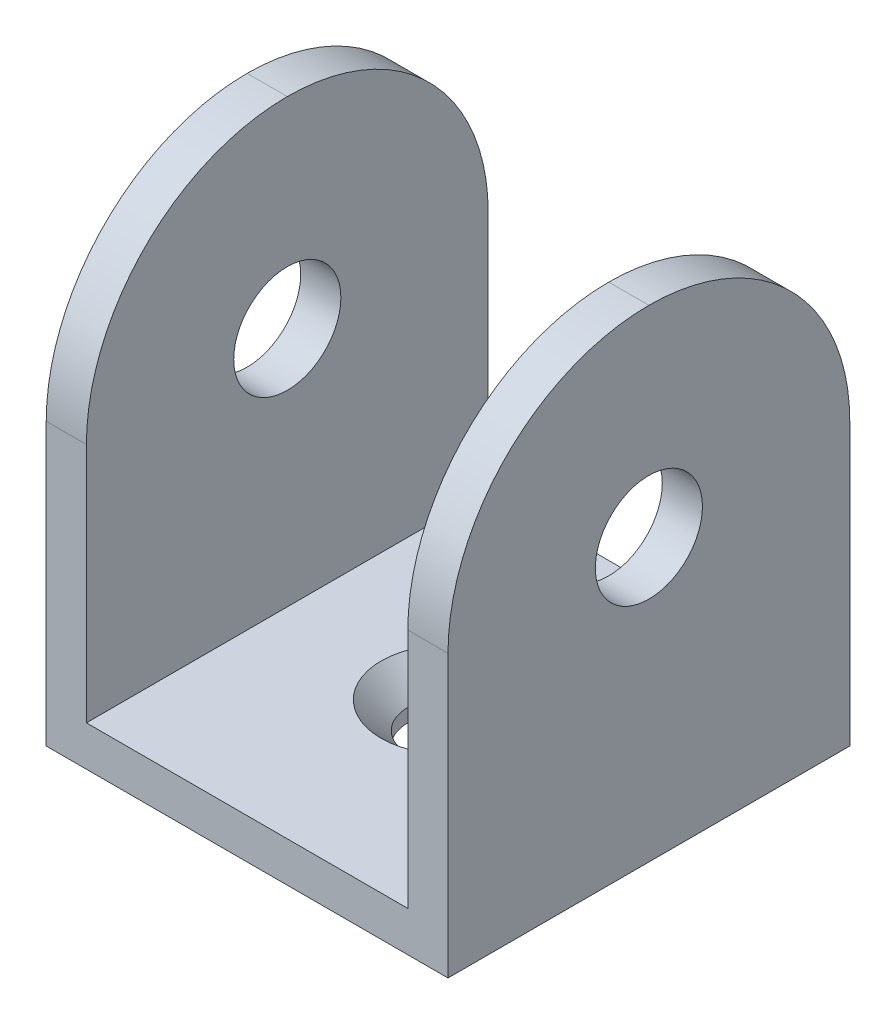
SolidWorks part; units mm, degrees
ref_plane "Alzado" through (0, 0, 0) normal (0, 0, 1) x (1, 0, 0)
ref_plane "Planta" through (0, 0, 0) normal (0, 1, 0) x (1, 0, 0)
ref_plane "Vista lateral" through (0, 0, 0) normal (1, 0, 0) x (0, 0, -1)
sketch "Croquis1" plane through (0, 0, 0) normal (0, 1, 0) x (1, 0, 0)
  line L1 (15, -15) -> (-15, -15)
  line L2 (15, -15) -> (15, 15)
  line L3 (15, 15) -> (-15, 15)
  line L4 (-15, -15) -> (-15, 15)
  line L5 (15, -15) -> (-15, 15) construction
  line L6 (15, 15) -> (-15, -15) construction
  point P0 (0, 0)
  dimension "D1" = 30
extrude "Saliente-Extruir1" add sketch "Croquis1" along normal blind 3
sketch "Croquis2" plane through (0, 3, 0) normal (0, 1, 0) x (1, 0, 0)
  line L0 (-15, -15) -> (15, -15) construction
  line L1 (-15, 15) -> (-12, 15)
  line L2 (-15, 15) -> (-15, -15)
  line L3 (-15, -15) -> (-12, -15)
  line L4 (-12, 15) -> (-12, -15)
  line L6 (15, 15) -> (12, 15)
  line L7 (15, 15) -> (15, -15)
  line L8 (15, -15) -> (12, -15)
  line L9 (12, 15) -> (12, -15)
  dimension "D1" = 3
extrude "Saliente-Extruir2" add sketch "Croquis2" along normal blind 33
fillet "Redondeo1" radius 15 4 edges at (-13.5, 36, -15) (13.5, 36, -15) (13.5, 36, 15) (-13.5, 36, 15)
sketch "Croquis3" plane through (15, 0, 0) normal (1, 0, 0) x (0, 0, -1)
  circle A0 centre (0, 21) radius 4
  dimension "D1" = 8
extrude "Cortar-Extruir1" cut sketch "Croquis3" against normal through all
sketch "Croquis4" plane through (0, 3, 0) normal (0, 1, 0) x (1, 0, 0)
  circle A0 centre (0, 0) radius 3
  dimension "D1" = 6
extrude "Cortar-Extruir2" cut sketch "Croquis4" against normal through all
chamfer "Chaflán1" distance 2 angle 45 1 edges at (0, 3, 3)
